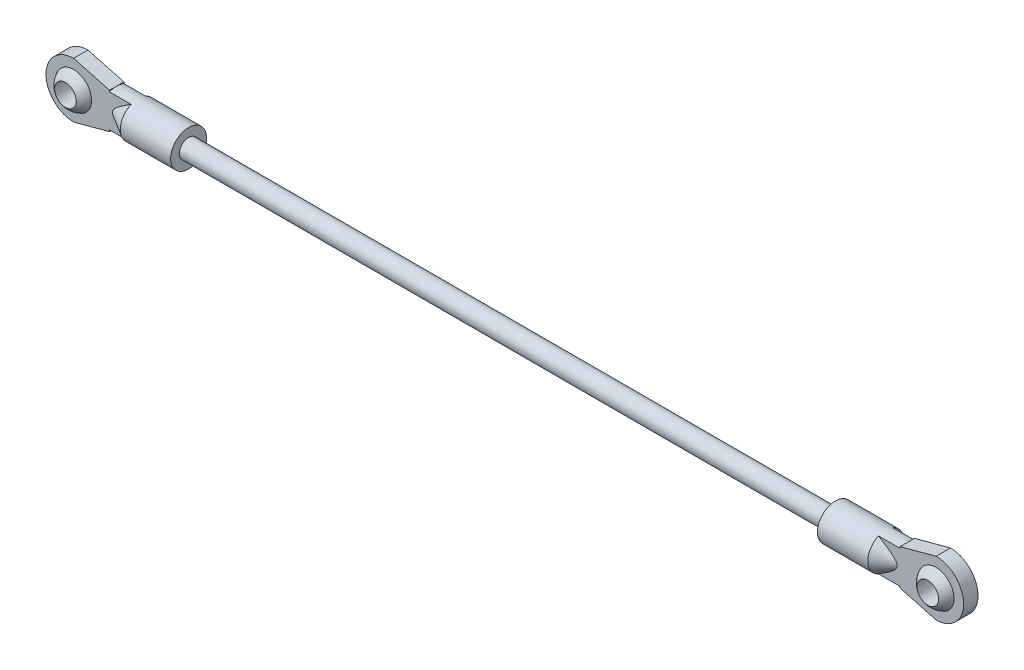
SolidWorks part; units mm, degrees
material "6063-T1"
ref_plane "前视基准面" through (0, 0, 0) normal (0, 0, 1) x (1, 0, 0)
ref_plane "上视基准面" through (0, 0, 0) normal (0, 1, 0) x (1, 0, 0)
ref_plane "右视基准面" through (0, 0, 0) normal (1, 0, 0) x (0, 0, -1)
other "Configuration Table"
sketch "草图1" plane through (0, 0, 0) normal (0, 0, 1) x (1, 0, 0)
  line L1 (0, 0) -> (90, 0)
  line L2 (0, 0) -> (0, 1.3)
  line L3 (0, 1.3) -> (90, 1.3)
  line L4 (90, 0) -> (90, 1.3)
  dimension "D1" = 90
  dimension "D2" = 1.3
revolve "旋转1" add sketch "草图1" angle 360 about L1
sketch "草图2" plane through (90, 0, 0) normal (1, 0, 0) x (0, 0, -1)
  circle A0 centre (0, 0) radius 2.5
  dimension "D1" = 5
extrude "凸台-拉伸1" add sketch "草图2" along normal blind 10
sketch "草图3" plane through (0, 0, 0) normal (-1, 0, 0) x (0, 0, 1)
  circle A0 centre (0, 0) radius 2.5
  dimension "D1" = 5
extrude "凸台-拉伸2" add sketch "草图3" along normal blind 10
sketch "草图4" plane through (0, 0, 0) normal (0, 0, 1) x (1, 0, 0)
  line L1 (100, -2.5) -> (100, 2.5) construction
  line L2 (108.8397, 0) -> (90, 0) construction
  line L3 (90, 2.5) -> (90, -2.5) construction
  line L4 (0, 0) -> (-18.8397, 0) construction
  line L5 (0, -1.3) -> (0, 1.3) construction
  line L6 (-10, -2.5) -> (0, -2.5) construction
  line L7 (90, -2.5) -> (100, -2.5) construction
  line L9 (100, 2.5) -> (100, -2.5)
  line L10 (-10, 2.5) -> (-15, 3.8397)
  line L11 (-15, 3.8397) -> (-15, -3.8397) construction
  line L12 (-15, -3.8397) -> (-10, -2.5)
  line L13 (-10, -2.5) -> (-10, 2.5)
  line L14 (100, 2.5) -> (105, 3.8397)
  line L15 (105, 3.8397) -> (105, -3.8397) construction
  line L16 (105, -3.8397) -> (100, -2.5)
  line L17 (0, 0) -> (90, 0) construction
  circle A2 centre (-15, 0) radius 1.55
  circle A3 centre (105, 0) radius 1.55
  arc A4 (-15, 3.8397) -> (-15, -3.8397) centre (-15, 0) ccw
  arc A5 (105, 3.8397) -> (105, -3.8397) centre (105, 0) cw
  point P6 (45, 0)
  point P31 (-46.8933, 17.5313)
  dimension "D3" = 3.1
  dimension "D4" = 3.1
  dimension "D2" = 105
  dimension "D1" = 60
  dimension "D5" = 60
  dimension "D6" = 105
  dimension "D7" = 105
  dimension "D8" = 105
extrude "凸台-拉伸3" add sketch "草图4" along normal blind 1 and the other way blind 1
sketch "草图5" plane through (0, 0, 0) normal (0, 0, 1) x (1, 0, 0)
  circle A0 centre (105, 0) radius 2.5
  circle A1 centre (-15, 0) radius 2.5
  dimension "D1" = 5
  dimension "D2" = 5
extrude "凸台-拉伸4" add sketch "草图5" along normal blind 2.5 and the other way blind 2.5
chamfer "倒角1" distance 3 angle 30 4 edges at (100, 0, -2.5) (100, 0, 2.5) (-10, 0, -2.5) (-10, 0, 2.5) first distance on face at (100, 0, 0) first distance on face at (-10, 0, 0)
fillet "圆角1" radius 2.5 4 edges at (107.5, 0, -2.5) (107.5, 0, 2.5) (-12.5, 0, 2.5) (-12.5, 0, -2.5)
sketch "草图6" plane through (0, 0, 0) normal (0, 0, 1) x (1, 0, 0)
  circle A0 centre (-15, 0) radius 1.5
  circle A1 centre (105, 0) radius 1.5
  dimension "D1" = 3
  dimension "D2" = 3
extrude "切除-拉伸1" cut sketch "草图6" against normal through all and the other way through all
